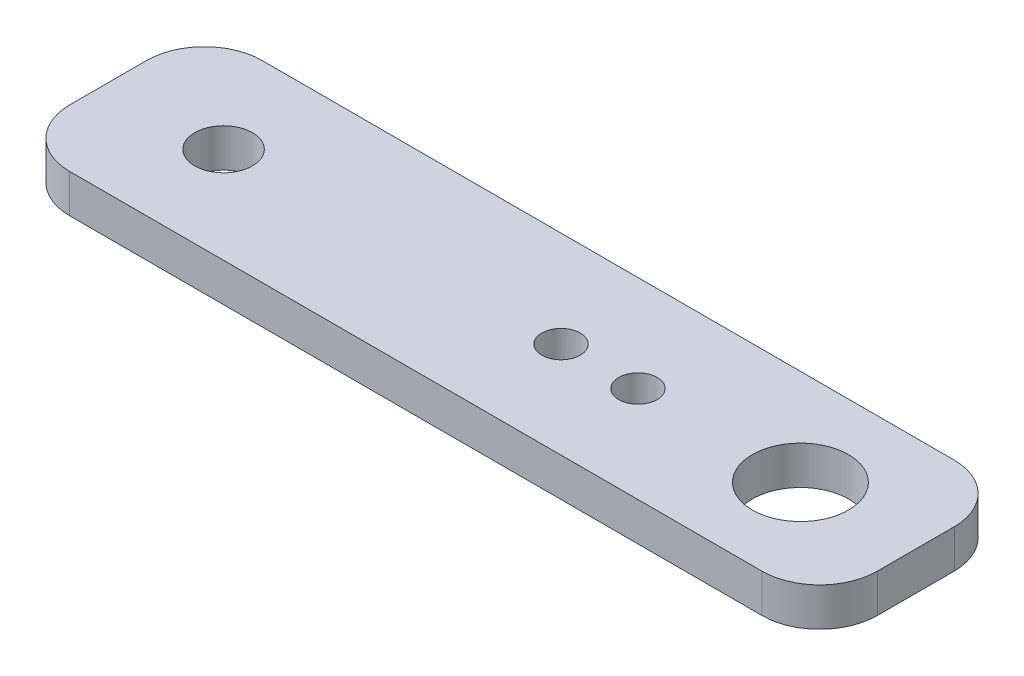
SolidWorks part; units mm, degrees
ref_plane "Front Plane" through (0, 0, 0) normal (0, 0, 1) x (1, 0, 0)
ref_plane "Top Plane" through (0, 0, 0) normal (0, 1, 0) x (1, 0, 0)
ref_plane "Right Plane" through (0, 0, 0) normal (1, 0, 0) x (0, 0, -1)
sketch "Sketch1" plane through (0, 0, 0) normal (0, 1, 0) x (1, 0, 0)
  line L1 (-21, 5) -> (21, 5)
  line L2 (-21, 5) -> (-21, -5)
  line L3 (-21, -5) -> (21, -5)
  line L4 (21, 5) -> (21, -5)
  line L5 (-21, 5) -> (21, -5) construction
  line L6 (-21, -5) -> (21, 5) construction
  point P0 (0, 0)
  dimension "D1" = 10
  dimension "D2" = 42
extrude "Boss-Extrude1" add sketch "Sketch1" along normal blind 2
hole_wizard "Ø5.0mm Dowel Hole1" positions "Sketch5" profile "Sketch6" hole size "Ø5.0" standard "ISO" end condition through all
sketch "Sketch5" plane through (0, 2, 0) normal (0, 1, 0) x (1, 0, 0)
  line L0 (21, -5) -> (21, 5) construction
  point P0 (15, 0)
  point P1 (0, 0)
  dimension "D1" = 6
sketch "Sketch6" plane through (15, 2, 0) normal (1, 0, 0) x (0, 0, 1)
  line L0 (0, 0) -> (0, 2)
  line L1 (0, 2) -> (2.5, 2)
  line L2 (2.5, 2) -> (2.5, 0)
  line L5 (2.5, 0) -> (0, 0)
  line L11 (0, -6.35) -> (0, 107.95) construction
  dimension "Thru Hole Dia." = 5
  dimension "Thru Hole Depth" = 2
hole_wizard "Ø3.0mm Dowel Hole1" positions "Sketch3" profile "Sketch4" hole size "Ø3.0" standard "ISO" end condition through all
sketch "Sketch3" plane through (0, 2, 0) normal (0, 1, 0) x (1, 0, 0)
  circle A4 centre (15, 0) radius 2.5 construction
  point P0 (-15, 0)
  dimension "D1" = 30
sketch "Sketch4" plane through (-15, 2, 0) normal (1, 0, 0) x (0, 0, 1)
  line L0 (0, 0) -> (0, 2)
  line L1 (0, 2) -> (1.5, 2)
  line L2 (1.5, 2) -> (1.5, 0)
  line L5 (1.5, 0) -> (0, 0)
  line L11 (0, -6.35) -> (0, 107.95) construction
  dimension "Thru Hole Dia." = 3
  dimension "Thru Hole Depth" = 2
sketch "Sketch2" plane through (0, 2, 0) normal (0, 1, 0) x (1, 0, 0)
  line L0 (15, 5) -> (15, -5) construction
  line L1 (-21, -5) -> (21, -5) construction
  line L3 (21, 0) -> (-21, 0) construction
  line L4 (21, -5) -> (21, 5) construction
  line L5 (-21, 5) -> (-21, -5) construction
  circle A3 centre (6.55, 0) radius 1
  circle A4 centre (2.55, 0) radius 1
  point P10 (15, 0)
  dimension "D1" = 2
  dimension "D2" = 8.45
  dimension "D3" = 4
extrude "Cut-Extrude1" cut sketch "Sketch2" against normal blind 3
fillet "Fillet1" radius 3 4 edges at (21, 1, 5) (21, 1, -5) (-21, 1, -5) (-21, 1, 5)
equation "\"globalength1\"=55"
